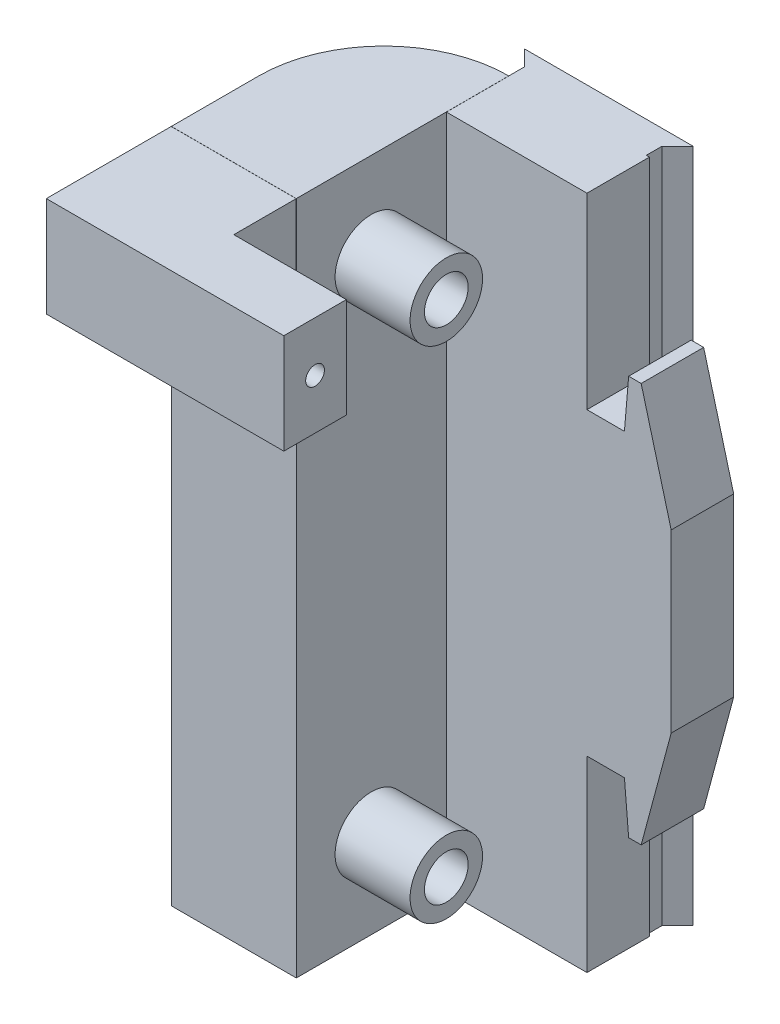
SolidWorks part; units mm, degrees
ref_plane "Front Plane" through (0, 0, 0) normal (0, 0, 1) x (1, 0, 0)
ref_plane "Top Plane" through (0, 0, 0) normal (0, 1, 0) x (1, 0, 0)
ref_plane "Right Plane" through (0, 0, 0) normal (1, 0, 0) x (0, 0, -1)
sketch "Sketch1" plane through (0, 0, 0) normal (1, 0, 0) x (0, 0, -1)
  line L1 (0, 0) -> (12, 0)
  line L2 (0, 0) -> (0, 54)
  line L3 (0, 54) -> (12, 54)
  line L4 (12, 0) -> (12, 54)
  dimension "D1" = 12
  dimension "D2" = 54
extrude "Boss-Extrude1" add sketch "Sketch1" along normal blind 10
sketch "Sketch2" plane through (0, 0, 0) normal (-1, 0, 0) x (0, 0, 1)
  line L0 (-12, 54) -> (0, 54) construction
  line L1 (0, 0) -> (-12, 0) construction
  line L2 (-12, 0) -> (-12, 54) construction
  circle A0 centre (-6, 47) radius 2.9
  circle A1 centre (-6, 7) radius 2.9
  dimension "D1" = 5.8
  dimension "D2" = 5.8
  dimension "D3" = 7
  dimension "D4" = 7
  dimension "D5" = 6
extrude "Boss-Extrude2" add sketch "Sketch2" along normal blind 18
sketch "Sketch3" plane through (-18, 0, 0) normal (-1, 0, 0) x (0, 0, 1)
  line L0 (-12, 0) -> (-12, 54) construction
  line L1 (-12, 0) -> (0, 0)
  line L2 (-12, 0) -> (-12, 54)
  line L3 (-12, 54) -> (0, 54)
  line L4 (0, 0) -> (0, 54)
  line L5 (-12, 54) -> (0, 54) construction
extrude "Boss-Extrude3" add sketch "Sketch3" along normal blind 10
sketch "Sketch4" plane through (10, 0, 0) normal (1, 0, 0) x (0, 0, -1)
  circle A0 centre (6, 47) radius 1.75
  circle A1 centre (6, 7) radius 1.75
  circle A2 centre (6, 47) radius 2.9 construction
  circle A3 centre (6, 7) radius 2.9 construction
  dimension "D1" = 3.5
  dimension "D2" = 3.5
extrude "Cut-Extrude1" cut sketch "Sketch4" against normal blind 50
sketch "Sketch5" plane through (0, 0, -12) normal (0, 0, -1) x (-1, 0, 0)
  line L1 (-10, 54) -> (28, 54)
  line L2 (-10, 54) -> (-10, 0)
  line L3 (-10, 0) -> (28, 0)
  line L4 (28, 54) -> (28, 0)
extrude "Boss-Extrude4" add sketch "Sketch5" along normal blind 5
fillet "Fillet1" radius 10 2 edges at (-28, 27, -17) (10, 27, -17)
sketch "Sketch6" plane through (0, 0, -12) normal (0, 0, 1) x (1, 0, 0)
  line L0 (0, 0) -> (-18, 0) construction
  line L1 (-6, 0) -> (-12, 0)
  line L2 (-6, 0) -> (-6, 54)
  line L3 (-6, 54) -> (-12, 54)
  line L4 (-12, 0) -> (-12, 54)
  line L5 (-18, 54) -> (0, 54) construction
  line L6 (-18, 54) -> (-18, 0) construction
  dimension "D1" = 6
  dimension "D2" = 6
extrude "Cut-Extrude2" cut sketch "Sketch6" along normal blind 15
sketch "Sketch7" plane through (0, 0, -12) normal (0, 0, 1) x (1, 0, 0)
  line L0 (0, 0) -> (-18, 0) construction
  line L1 (-18, 54) -> (-17.99, 54)
  line L2 (-18, 54) -> (-18, 0)
  line L3 (-18, 0) -> (-17.99, 0)
  line L4 (-17.99, 54) -> (-17.99, 0)
  line L5 (-18, 54) -> (0, 54) construction
  line L6 (0, 0) -> (-0.01, 0)
  line L7 (0, 0) -> (0, 54)
  line L8 (0, 54) -> (-0.01, 54)
  line L9 (-0.01, 0) -> (-0.01, 54)
  dimension "D1" = 0.01
  dimension "D2" = 0.01
extrude "Cut-Extrude3" cut sketch "Sketch7" against normal blind 12.5
sketch "Sketch8" plane through (0, 54, 0) normal (0, 1, 0) x (1, 0, 0)
  line L0 (-18, 0) -> (-18, -5)
  line L1 (-18, -5) -> (0, -5)
  line L2 (0, -5) -> (0, 0)
  line L3 (0, 0) -> (10, 0)
  line L4 (10, 0) -> (10, -10)
  line L5 (10, -10) -> (-28, -10)
  line L6 (-28, -10) -> (-28, 0)
  line L7 (-28, 0) -> (-18, 0)
  dimension "D1" = 5
  dimension "D2" = 10
extrude "Boss-Extrude5" add sketch "Sketch8" against normal blind 8
sketch "Sketch9" plane through (0, 46, 0) normal (0, -1, 0) x (1, 0, 0)
  line L0 (-28, 0) -> (-28, 10) construction
  line L1 (10, 0) -> (-28, 0)
  line L2 (10, 0) -> (10, 0.01)
  line L3 (10, 0.01) -> (-28, 0.01)
  line L4 (-28, 0) -> (-28, 0.01)
  dimension "D1" = 0.01
extrude "Cut-Extrude4" cut sketch "Sketch9" against normal blind 50
sketch "Sketch10" plane through (0, 0, -17) normal (0, 0, -1) x (-1, 0, 0)
  line L0 (17.99, 54) -> (0.01, 54) construction
  line L1 (7, 54) -> (18, 54)
  line L2 (7, 54) -> (7, 0)
  line L3 (7, 0) -> (18, 0)
  line L4 (18, 54) -> (18, 0)
  dimension "D1" = 11
extrude "Boss-Extrude6" add sketch "Sketch10" along normal blind 2.5
sketch "Sketch11" plane through (0, 54, 0) normal (0, 1, 0) x (1, 0, 0)
  line L0 (-18, 18.25) -> (-19.25, 19.5)
  line L1 (-18, 19.5) -> (-18, 17) construction
  line L2 (-19.25, 19.5) -> (-18, 19.5)
  line L3 (-18, 19.5) -> (-18, 18.25)
  line L4 (-7, 19.5) -> (-7, 18.25)
  line L5 (-7, 19.5) -> (-7, 17) construction
  line L6 (-7, 18.25) -> (-5.75, 19.5)
  line L7 (-5.75, 19.5) -> (-7, 19.5)
extrude "Boss-Extrude7" add sketch "Sketch11" against normal blind 54
sketch "Sketch13" plane through (0, 0, -17) normal (0, 0, -1) x (-1, 0, 0)
  line L0 (0.01, 54) -> (5.75, 54)
  line L2 (0, 34) -> (0, 20)
  line L3 (4.75, 39) -> (5.75, 39)
  line L4 (0.01, 0) -> (0.01, 54) construction
  line L5 (0.01, 54) -> (0, 34)
  line L6 (0, 54) -> (0, 0) construction
  line L7 (0, 34) -> (2.4125, 42.9857)
  line L8 (2.4125, 42.9857) -> (3.4125, 42.9857)
  line L10 (4.75, 15) -> (5.75, 15)
  line L11 (5.75, 0) -> (5.75, -8.3022)
  line L12 (5.75, -8.3022) -> (-24.0506, -8.3022)
  line L13 (-24.0506, -8.3022) -> (-24.0506, 57.5316)
  line L14 (-24.0506, 57.5316) -> (5.75, 57.5316)
  line L15 (0, 20) -> (2.4125, 11.0143)
  line L16 (2.4125, 11.0143) -> (3.4125, 11.0143)
  line L19 (5.75, 0) -> (0.01, 0)
  line L20 (0.01, 0) -> (0, 20)
  line L21 (5.75, 57.5316) -> (5.75, 54)
  line L22 (5.75, 39) -> (6.75, 39)
  line L23 (6.75, 39) -> (6.75, 54)
  line L24 (19.25, 54) -> (5.75, 54) construction
  line L25 (6.75, 54) -> (5.75, 54)
  line L26 (5.75, 15) -> (6.75, 15)
  line L27 (6.75, 15) -> (6.75, 0)
  line L28 (6.75, 0) -> (5.75, 0)
  line L29 (3.4125, 42.9857) -> (3.75, 39)
  line L30 (3.75, 39) -> (4.75, 39)
  line L31 (3.4125, 11.0143) -> (3.75, 15)
  line L32 (3.75, 15) -> (4.75, 15)
  dimension "D1" = 20
  dimension "D2" = 15
  dimension "D5" = 1
  dimension "D6" = 15
  dimension "D7" = 1
extrude "Cut-Extrude5" cut sketch "Sketch13" against normal up to surface (5 mm away)
sketch "Sketch14" plane through (0, 0, 10) normal (0, 0, 1) x (1, 0, 0)
  line L0 (-28, 54) -> (10, 54) construction
  line L1 (-9, 54) -> (23.8873, 54)
  line L2 (-9, 54) -> (-9, -5.6832)
  line L3 (-9, -5.6832) -> (23.8873, -5.6832)
  line L4 (23.8873, 54) -> (23.8873, -5.6832)
extrude "Cut-Extrude6" cut sketch "Sketch14" against normal up to surface (22 mm away) up to face at (-5.8679, 27, -12)
sketch "Sketch15" plane through (-9, 0, 0) normal (1, 0, 0) x (0, 0, -1)
  line L0 (-10, 54) -> (-5, 46) construction
  line L1 (-5, 54) -> (-10, 46) construction
  circle A0 centre (-7.5, 50) radius 0.75
  dimension "D1" = 1.5
extrude "Cut-Extrude7" cut sketch "Sketch15" against normal blind 5
